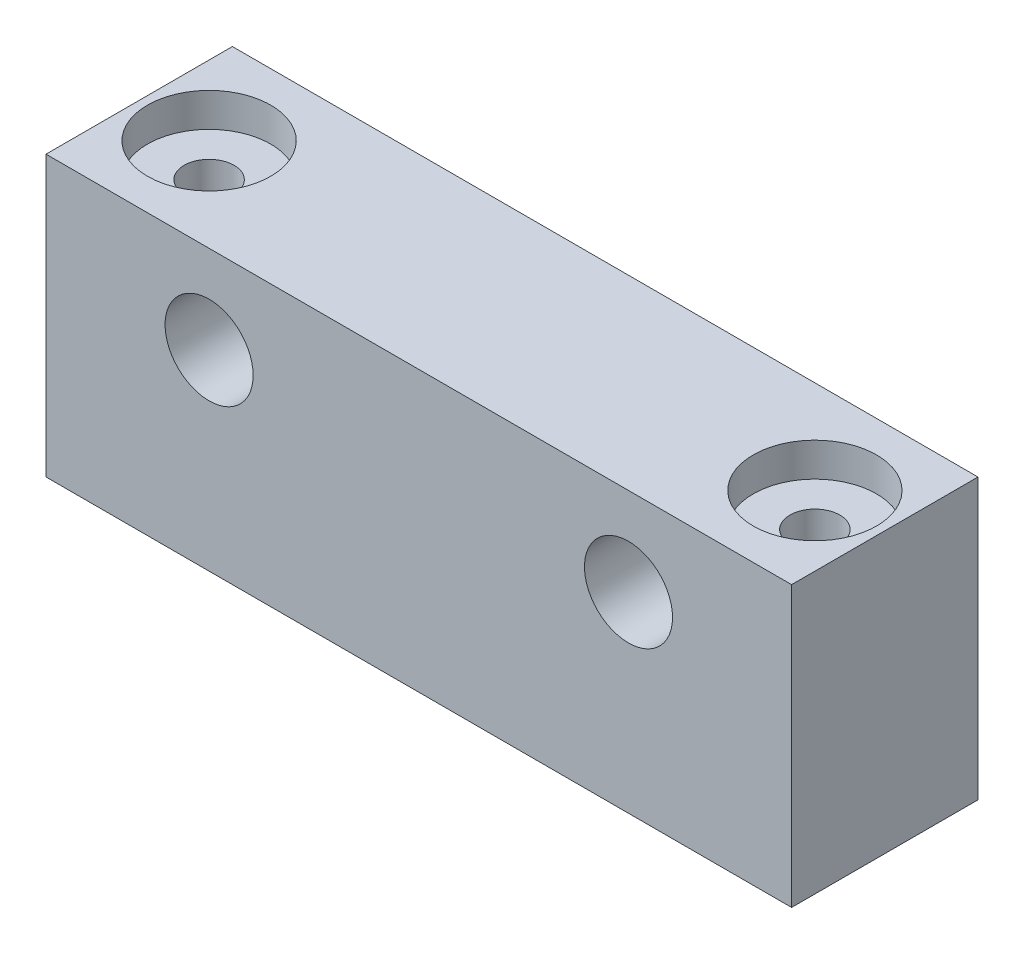
SolidWorks part; units mm, degrees
material "AISI 304"
ref_plane "Front Plane" through (0, 0, 0) normal (0, 0, 1) x (1, 0, 0)
ref_plane "Top Plane" through (0, 0, 0) normal (0, 1, 0) x (1, 0, 0)
ref_plane "Right Plane" through (0, 0, 0) normal (1, 0, 0) x (0, 0, -1)
sketch "Sketch1" plane through (0, 0, 0) normal (0, 0, 1) x (1, 0, 0)
  line L0 (0, 0) -> (0, 29.3284) construction
  line L1 (-25.4, -9.525) -> (25.4, -9.525)
  line L2 (-25.4, -9.525) -> (-25.4, 9.525)
  line L3 (-25.4, 9.525) -> (25.4, 9.525)
  line L4 (25.4, -9.525) -> (25.4, 9.525)
  line L5 (-25.4, -9.525) -> (25.4, 9.525) construction
  line L6 (-25.4, 9.525) -> (25.4, -9.525) construction
  line L7 (-14.2875, 3.525) -> (14.2875, 3.525) construction
  circle A0 centre (-14.2875, 3.525) radius 3
  circle A1 centre (14.2875, 3.525) radius 3
  point P0 (0, 0)
  point P13 (0, 3.525)
  dimension "D3" = 6
  dimension "D4" = 6
  dimension "D1" = 19.05
  dimension "D2" = 50.8
  dimension "D5" = 28.575
  dimension "D6" = 6
extrude "Boss-Extrude1" add sketch "Sketch1" along normal blind 12.7
hole_wizard "CBORE for M3 Hex Head Machine Screw1" positions "Sketch2" profile "Sketch4" counterbore size "M3" standard "ANSI Metric" end condition through all
sketch "Sketch2" plane through (0, 9.525, 0) normal (0, 1, 0) x (1, 0, 0)
  line L6 (-25.4, -12.7) -> (-25.4, 0) construction
  line L7 (-20.6375, -6.35) -> (20.6375, -6.35) construction
  point P0 (-20.6375, -6.35)
  point P2 (20.6375, -6.35)
  point P29 (-25.4, -6.35)
  point P38 (0, -6.35)
  dimension "D1" = 41.275
sketch "Sketch4" plane through (-20.6375, 9.525, 6.35) normal (1, 0, 0) x (0, 0, 1)
  line L0 (0, 0) -> (0, 19.05)
  line L1 (0, 19.05) -> (1.7, 19.05)
  line L3 (1.7, 19.05) -> (1.7, 2.3)
  line L4 (1.7, 2.3) -> (4.2, 2.3)
  line L5 (4.2, 2.3) -> (4.2, 0)
  line L7 (4.2, 0) -> (0, 0)
  line L11 (0, -6.35) -> (0, 107.95) construction
  dimension "Thru Hole Dia." = 3.4
  dimension "Thru Hole Depth" = 19.05
  dimension "C'Bore Dia." = 8.4
  dimension "C'Bore Depth" = 2.3
